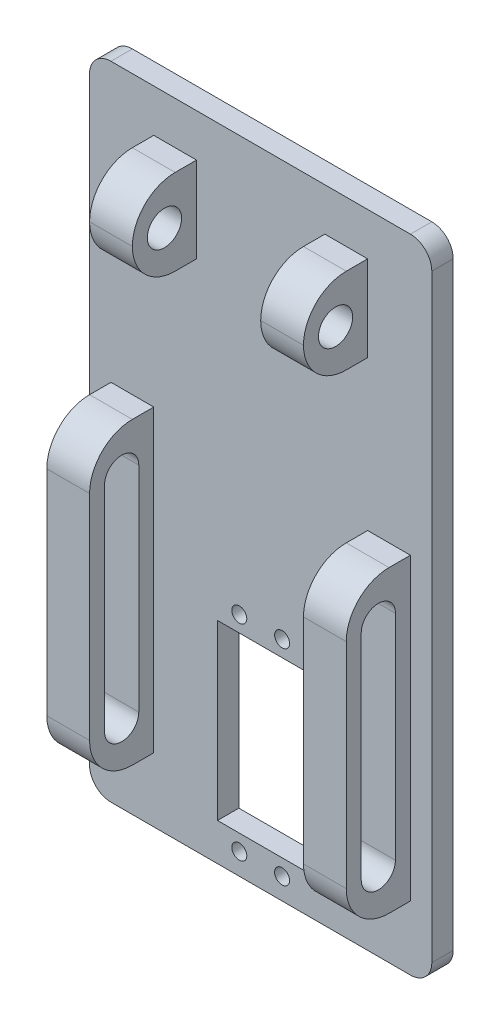
SolidWorks part; units mm, degrees
ref_plane "前视基准面" through (0, 0, 0) normal (0, 0, 1) x (1, 0, 0)
ref_plane "上视基准面" through (0, 0, 0) normal (0, 1, 0) x (1, 0, 0)
ref_plane "右视基准面" through (0, 0, 0) normal (1, 0, 0) x (0, 0, -1)
sketch "草图1" plane through (0, 0, 0) normal (0, 0, 1) x (1, 0, 0)
  line L0 (-35, -60) -> (-25, -60) construction
  line L1 (35, -75) -> (-35, -75)
  line L2 (40, -70) -> (40, 70)
  line L3 (35, 75) -> (-35, 75)
  line L4 (-40, -70) -> (-40, 70)
  line L5 (0, 75) -> (0, -75) construction
  line L6 (40, 0) -> (-40, 0) construction
  line L7 (25, 45) -> (15, 45) construction
  line L8 (25, 45) -> (25, 65) construction
  line L9 (25, 65) -> (15, 65) construction
  line L10 (15, 45) -> (15, 65) construction
  line L11 (20, 65) -> (20, 45) construction
  line L12 (25, 55) -> (15, 55) construction
  line L13 (35, -60) -> (25, -60) construction
  line L14 (35, -60) -> (35, 10) construction
  line L15 (35, 10) -> (25, 10) construction
  line L16 (25, -60) -> (25, 10) construction
  line L17 (30, 10) -> (30, -60) construction
  line L18 (35, -25) -> (25, -25) construction
  line L19 (-35, -60) -> (-35, 10) construction
  line L20 (-35, 10) -> (-25, 10) construction
  line L21 (-25, -60) -> (-25, 10) construction
  line L22 (-25, 45) -> (-25, 65) construction
  line L23 (-25, 45) -> (-15, 45) construction
  line L24 (-25, 65) -> (-15, 65) construction
  line L25 (-15, 45) -> (-15, 65) construction
  line L26 (15.1, -66.25) -> (15.1, -25.75) construction
  line L27 (15.1, -25.75) -> (-5.1, -25.75) construction
  line L28 (-5.1, -25.75) -> (-5.1, -66.25) construction
  line L29 (-5.1, -66.25) -> (15.1, -66.25) construction
  line L30 (15.1, -66.25) -> (15.1, -25.75) construction
  line L31 (15.1, -25.75) -> (-5.1, -25.75) construction
  line L32 (-5.1, -25.75) -> (-5.1, -66.25) construction
  line L33 (-5.1, -66.25) -> (15.1, -66.25) construction
  line L34 (10.1, -25.75) -> (-10.1, -25.75)
  line L35 (-10.1, -25.75) -> (-10.1, -66.25)
  line L36 (-10.1, -66.25) -> (10.1, -66.25)
  line L37 (10.1, -66.25) -> (10.1, -25.75)
  line L38 (-10.1, -46) -> (10.1, -46) construction
  arc A0 (35, -75) -> (40, -70) centre (35, -70) ccw
  arc A1 (40, 70) -> (35, 75) centre (35, 70) ccw
  arc A2 (-35, -75) -> (-40, -70) centre (-35, -70) cw
  arc A3 (-35, 75) -> (-40, 70) centre (-35, 70) ccw
  circle A19 centre (0, -70) radius 1.65 construction
  circle A20 centre (0, -22) radius 1.75 construction
  circle A21 centre (10, -22) radius 1.75 construction
  circle A22 centre (10, -70) radius 1.75 construction
  circle A23 centre (0, -22) radius 1.75 construction
  circle A24 centre (10, -22) radius 1.75 construction
  circle A25 centre (10, -70) radius 1.75 construction
  circle A26 centre (-5, -22) radius 1.75
  circle A27 centre (5, -22) radius 1.75
  circle A28 centre (5, -70) radius 1.75
  circle A29 centre (-5, -70) radius 1.75
  point P0 (0, 0)
  point P4 (20, 55)
  point P11 (30, -25)
  point P32 (40, -75)
  point P35 (40, 75)
  point P40 (-40, 75)
  point P88 (0, -25.75)
  dimension "D10" = 5
  dimension "D14" = 3.3
  dimension "D17" = 3.5
  dimension "D1" = 80
  dimension "D2" = 150
  dimension "D3" = 10
  dimension "D4" = 20
  dimension "D5" = 10
  dimension "D6" = 70
  dimension "D7" = 15
  dimension "D8" = 5
  dimension "D9" = 10
  dimension "D15" = 3.75
  dimension "D16" = 20.2
  dimension "D18" = 5
extrude "凸台-拉伸1" add sketch "草图1" along normal blind 5
sketch "草图2" plane through (0, 0, 5) normal (0, 0, 1) x (1, 0, 0)
  line L0 (25, 45) -> (25, 65) construction
  line L1 (25, 45) -> (15, 45) construction
  line L2 (25, 65) -> (15, 65) construction
  line L3 (15, 45) -> (15, 65) construction
  line L4 (35, -60) -> (25, -60) construction
  line L5 (35, -60) -> (35, 10) construction
  line L6 (35, 10) -> (25, 10) construction
  line L7 (25, -60) -> (25, 10) construction
  line L8 (-35, -60) -> (-25, -60) construction
  line L9 (-25, -60) -> (-25, 10) construction
  line L10 (-35, -60) -> (-35, 10) construction
  line L11 (-35, 10) -> (-25, 10) construction
  line L12 (-25, 45) -> (-15, 45) construction
  line L13 (-15, 45) -> (-15, 65) construction
  line L14 (-25, 65) -> (-15, 65) construction
  line L15 (-25, 45) -> (-25, 65) construction
  line L16 (25, 45) -> (25, 65)
  line L17 (25, 45) -> (15, 45)
  line L18 (25, 65) -> (15, 65)
  line L19 (15, 45) -> (15, 65)
  line L20 (35, -60) -> (25, -60)
  line L21 (35, -60) -> (35, 10)
  line L22 (35, 10) -> (25, 10)
  line L23 (25, -60) -> (25, 10)
  line L24 (-35, -60) -> (-25, -60)
  line L25 (-25, -60) -> (-25, 10)
  line L26 (-35, -60) -> (-35, 10)
  line L27 (-35, 10) -> (-25, 10)
  line L28 (-25, 45) -> (-15, 45)
  line L29 (-15, 45) -> (-15, 65)
  line L30 (-25, 65) -> (-15, 65)
  line L31 (-25, 45) -> (-25, 65)
extrude "凸台-拉伸2" add sketch "草图2" along normal blind 15
sketch "草图3" plane through (-35, 0, 0) normal (-1, 0, 0) x (0, 0, 1)
  line L0 (20, -25) -> (5, -25) construction
  line L1 (20, 10) -> (20, -60) construction
  line L2 (5, 10) -> (5, -60) construction
  line L3 (12.5, -50) -> (12.5, 0) construction
  line L4 (12.5, -50) -> (12.5, 0) construction
  line L5 (8.5, -50) -> (8.5, 0)
  line L6 (16.5, -50) -> (16.5, 0)
  circle A0 centre (12.5, 55) radius 4
  arc A1 (8.5, -50) -> (16.5, -50) centre (12.5, -50) ccw
  arc A2 (16.5, 0) -> (8.5, 0) centre (12.5, 0) ccw
  point P8 (12.5, -25)
  point P11 (12.5, -25)
  dimension "D1" = 8
  dimension "D2" = 50
  dimension "D3" = 8
extrude "切除-拉伸1" cut sketch "草图3" against normal blind 146
fillet "圆角1" radius 10 8 edges at (30, -60, 20) (-30, -60, 20) (30, 10, 20) (-30, 10, 20) (20, 45, 20) (20, 65, 20) (-20, 45, 20) (-20, 65, 20)
